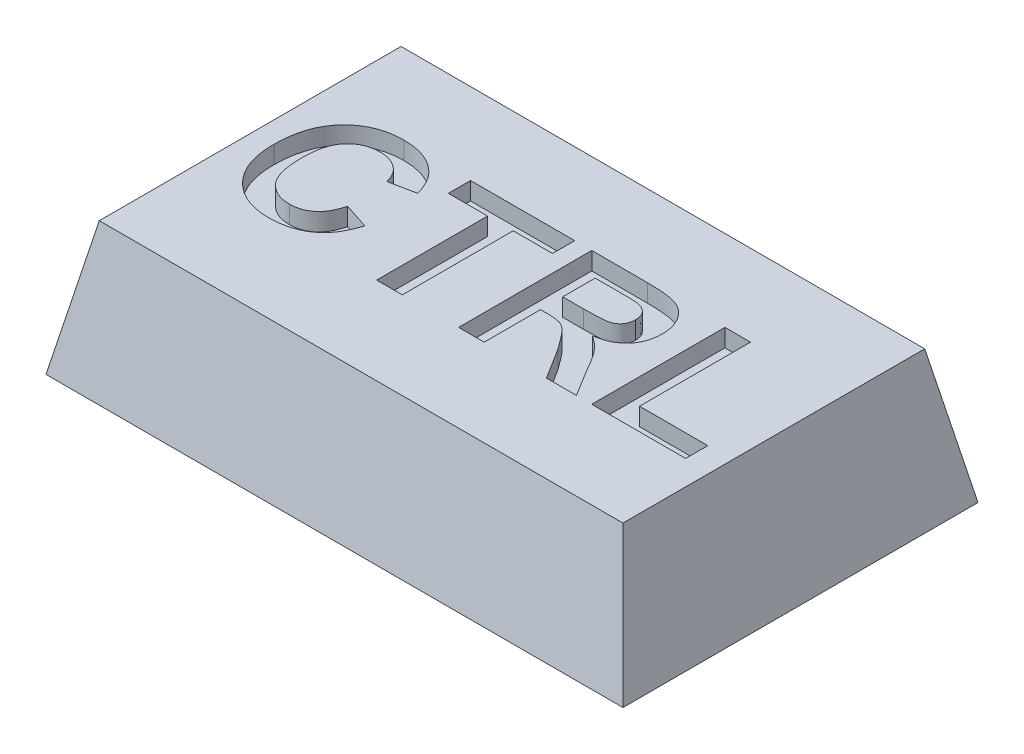
SolidWorks part; units mm, degrees
ref_plane "Front Plane" through (0, 0, 0) normal (0, 0, 1) x (1, 0, 0)
ref_plane "Top Plane" through (0, 0, 0) normal (0, 1, 0) x (1, 0, 0)
ref_plane "Right Plane" through (0, 0, 0) normal (1, 0, 0) x (0, 0, -1)
sketch "Sketch1" plane through (0, 0, 0) normal (0, 1, 0) x (1, 0, 0)
  line L1 (0, 0) -> (13, 0)
  line L2 (0, 0) -> (0, 8)
  line L3 (0, 8) -> (13, 8)
  line L4 (13, 0) -> (13, 8)
  dimension "D1" = 8
  dimension "D2" = 13
extrude "Boss-Extrude1" add sketch "Sketch1" along normal blind 3
sketch "Sketch2" plane through (0, 0, 0) normal (0, 0, 1) x (1, 0, 0)
  line L0 (0, 0) -> (0.6, 3)
  line L1 (0, 3) -> (13, 3) construction
  line L2 (0.6, 3) -> (0, 3)
  line L3 (0, 3) -> (0, 0)
  line L4 (13, 0) -> (12.4, 3)
  line L5 (12.4, 3) -> (13, 3)
  line L6 (13, 3) -> (13, 0)
  dimension "D1" = 0.6
  dimension "D2" = 0.6
extrude "Cut-Extrude1" cut sketch "Sketch2" against normal through all both and the other way through all
sketch "Sketch3" plane through (0, 0, 0) normal (1, 0, 0) x (0, 0, -1)
  line L0 (0, 0) -> (0.6, 3)
  line L1 (8, 3) -> (0, 3) construction
  line L2 (0.6, 3) -> (0, 3)
  line L3 (0, 3) -> (0, 0)
  line L4 (8, 3) -> (7.4, 3)
  line L5 (7.4, 3) -> (8, 0)
  line L6 (8, 3) -> (8, 0)
  dimension "D1" = 0.6
  dimension "D2" = 0.6
extrude "Cut-Extrude2" cut sketch "Sketch3" along normal through all both and the other way through all
sketch "Sketch4" plane through (0, 0, 0) normal (0, -1, 0) x (1, 0, 0)
  line L1 (6.5, 0) -> (6.5, -8) construction
  line L2 (13, -8) -> (0, -8) construction
  line L3 (0, 0) -> (13, 0) construction
  circle A0 centre (6.5, -3.75) radius 1.75
  dimension "D1" = 3.5
  dimension "D2" = 0
  dimension "D3" = 3.75
extrude "Cut-Extrude3" cut sketch "Sketch4" against normal blind 0.4
sketch "Sketch5" plane through (0, 0, 0) normal (0, -1, 0) x (1, 0, 0)
  line L5 (0, 0) -> (13, 0) construction
  line L6 (2.5, -8) -> (10.5, -8)
  line L7 (2.5, -8) -> (2.5, -6.9)
  line L8 (2.5, -6.9) -> (10.5, -6.9)
  line L9 (10.5, -8) -> (10.5, -6.9)
  point P2 (6.5, 0)
  dimension "D1" = 1.1
  dimension "D2" = 4
  dimension "D3" = 4
extrude "Boss-Extrude2" add sketch "Sketch5" along normal blind 2
fillet "Fillet1" radius 4 2 edges at (10.5, -2, -7.45) (2.5, -2, -7.45)
sketch "Sketch6" plane through (0, 3, 0) normal (0, 1, 0) x (1, 0, 0)
  text T0 "CTRL" font "Arial" height 3
extrude "Cut-Extrude4" cut sketch "Sketch6" against normal blind 0.4
